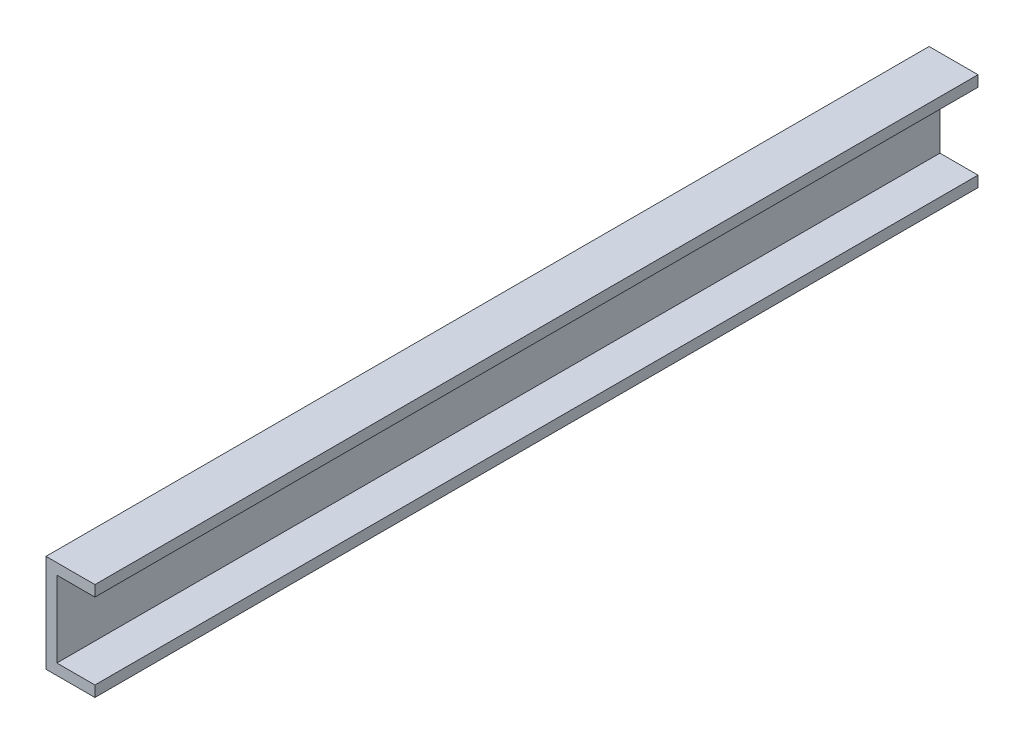
SolidWorks part; units mm, degrees
ref_plane "Front Plane" through (0, 0, 0) normal (0, 0, 1) x (1, 0, 0)
ref_plane "Top Plane" through (0, 0, 0) normal (0, 1, 0) x (1, 0, 0)
ref_plane "Right Plane" through (0, 0, 0) normal (1, 0, 0) x (0, 0, -1)
sketch "Sketch1" plane through (0, 0, 0) normal (0, 0, 1) x (1, 0, 0)
  line L0 (0, 9) -> (0, -9)
  line L1 (0, -9) -> (9, -9)
  line L2 (0, 9) -> (9, 9)
  line L3 (2, -7) -> (9, -7)
  line L4 (2, 7) -> (2, -7)
  line L5 (2, 7) -> (9, 7)
  line L6 (9, -9) -> (9, -7)
  line L7 (9, 9) -> (9, 7)
  dimension "D1" = 18
  dimension "D2" = 9
  dimension "D3" = 9
  dimension "D4" = 9
  dimension "D5" = 2
extrude "Boss-Extrude1" add sketch "Sketch1" against normal blind 162.5
